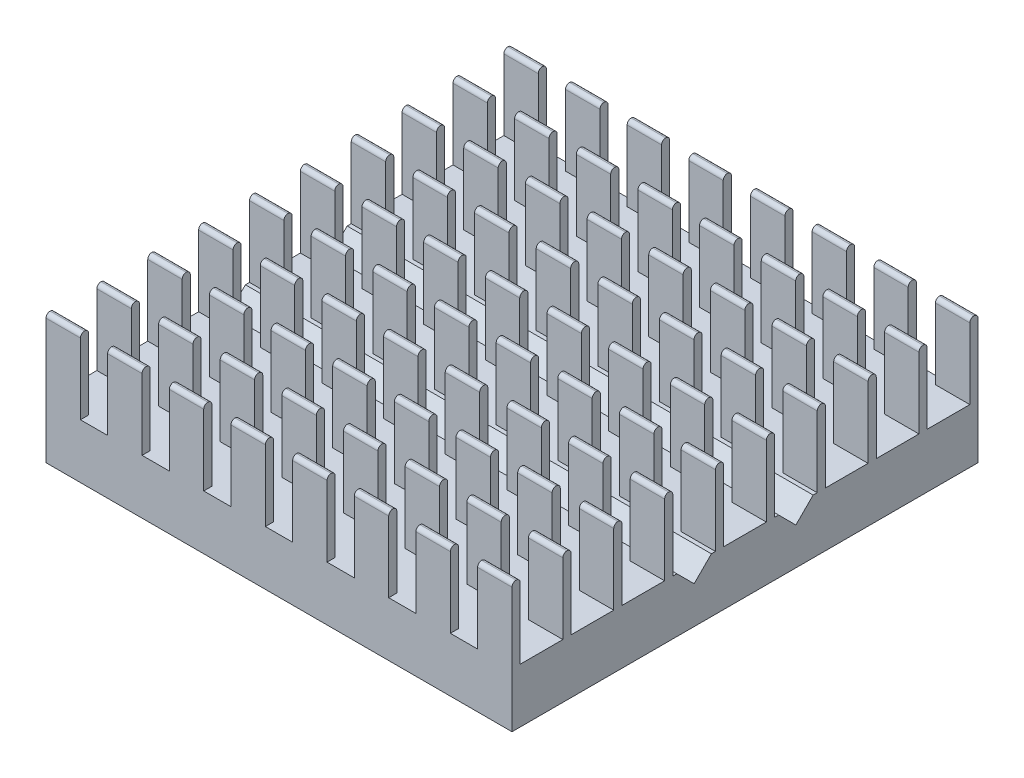
SolidWorks part; units mm, degrees
ref_plane "Front Plane" through (0, 0, 0) normal (0, 0, 1) x (1, 0, 0)
ref_plane "Top Plane" through (0, 0, 0) normal (0, 1, 0) x (1, 0, 0)
ref_plane "Right Plane" through (0, 0, 0) normal (1, 0, 0) x (0, 0, -1)
sketch "Sketch1" plane through (0, 0, 0) normal (1, 0, 0) x (0, 0, -1)
  line L0 (-17.125, -0.75) -> (17.125, -0.75) construction
  line L1 (-17.125, 4.75) -> (17.125, 4.75)
  line L2 (-17.125, 4.75) -> (-17.125, -4.75)
  line L3 (-17.125, -4.75) -> (17.125, -4.75)
  line L4 (17.125, 4.75) -> (17.125, -4.75)
  point P4 (-17.125, 0)
  point P6 (0, 4.75)
  dimension "Overall Length" = 34.25
  dimension "Overall Height" = 9.5
  dimension "Base Height" = 4
sketch "Sketch2" plane through (0, 0, 0) normal (0, 1, 0) x (1, 0, 0)
  line L0 (-12.5936, -16.525) -> (-10.0636, -16.525)
  line L1 (-17.125, 17.125) -> (17.125, 17.125) construction
  line L2 (-17.125, 17.125) -> (-17.125, -17.125) construction
  line L3 (-17.125, -17.125) -> (17.125, -17.125) construction
  line L4 (17.125, 17.125) -> (17.125, -17.125) construction
  line L5 (-17.125, -16.525) -> (-14.595, -16.525)
  line L6 (-17.125, -16.525) -> (-17.125, -17.125)
  line L7 (-17.125, -17.125) -> (-14.595, -17.125)
  line L8 (-14.595, -16.525) -> (-14.595, -17.125)
  line L9 (-12.5936, -16.525) -> (-12.5936, -17.125)
  line L10 (-12.5936, -17.125) -> (-10.0636, -17.125)
  line L11 (-10.0636, -16.525) -> (-10.0636, -17.125)
  line L12 (-8.0621, -16.525) -> (-5.5321, -16.525)
  line L13 (-8.0621, -16.525) -> (-8.0621, -17.125)
  line L14 (-8.0621, -17.125) -> (-5.5321, -17.125)
  line L15 (-5.5321, -16.525) -> (-5.5321, -17.125)
  line L16 (-12.5936, -12.7861) -> (-10.0636, -12.7861)
  line L17 (-12.5936, -12.7861) -> (-12.5936, -13.3861)
  line L18 (-12.5936, -13.3861) -> (-10.0636, -13.3861)
  line L19 (-10.0636, -12.7861) -> (-10.0636, -13.3861)
  line L20 (-8.0621, -12.7861) -> (-5.5321, -12.7861)
  line L21 (-8.0621, -12.7861) -> (-8.0621, -13.3861)
  line L22 (-8.0621, -13.3861) -> (-5.5321, -13.3861)
  line L23 (-5.5321, -12.7861) -> (-5.5321, -13.3861)
  line L24 (-12.5936, -9.0472) -> (-10.0636, -9.0472)
  line L25 (-12.5936, -9.0472) -> (-12.5936, -9.6472)
  line L26 (-12.5936, -9.6472) -> (-10.0636, -9.6472)
  line L27 (-10.0636, -9.0472) -> (-10.0636, -9.6472)
  line L28 (-8.0621, -9.0472) -> (-5.5321, -9.0472)
  line L29 (-8.0621, -9.0472) -> (-8.0621, -9.6472)
  line L30 (-8.0621, -9.6472) -> (-5.5321, -9.6472)
  line L31 (-5.5321, -9.0472) -> (-5.5321, -9.6472)
  line L32 (-12.5936, -5.3083) -> (-10.0636, -5.3083)
  line L33 (-12.5936, -5.3083) -> (-12.5936, -5.9083)
  line L34 (-12.5936, -5.9083) -> (-10.0636, -5.9083)
  line L35 (-10.0636, -5.3083) -> (-10.0636, -5.9083)
  line L36 (-8.0621, -5.3083) -> (-5.5321, -5.3083)
  line L37 (-8.0621, -5.3083) -> (-8.0621, -5.9083)
  line L38 (-8.0621, -5.9083) -> (-5.5321, -5.9083)
  line L39 (-5.5321, -5.3083) -> (-5.5321, -5.9083)
  line L40 (-12.5936, -1.5694) -> (-10.0636, -1.5694)
  line L41 (-12.5936, -1.5694) -> (-12.5936, -2.1694)
  line L42 (-12.5936, -2.1694) -> (-10.0636, -2.1694)
  line L43 (-10.0636, -1.5694) -> (-10.0636, -2.1694)
  line L44 (-8.0621, -1.5694) -> (-5.5321, -1.5694)
  line L45 (-8.0621, -1.5694) -> (-8.0621, -2.1694)
  line L46 (-8.0621, -2.1694) -> (-5.5321, -2.1694)
  line L47 (-5.5321, -1.5694) -> (-5.5321, -2.1694)
  line L48 (-12.5936, 2.1694) -> (-10.0636, 2.1694)
  line L49 (-12.5936, 2.1694) -> (-12.5936, 1.5694)
  line L50 (-12.5936, 1.5694) -> (-10.0636, 1.5694)
  line L51 (-10.0636, 2.1694) -> (-10.0636, 1.5694)
  line L52 (-8.0621, 2.1694) -> (-5.5321, 2.1694)
  line L53 (-8.0621, 2.1694) -> (-8.0621, 1.5694)
  line L54 (-8.0621, 1.5694) -> (-5.5321, 1.5694)
  line L55 (-5.5321, 2.1694) -> (-5.5321, 1.5694)
  line L56 (-17.125, -12.7861) -> (-14.595, -12.7861)
  line L57 (-17.125, -12.7861) -> (-17.125, -13.3861)
  line L58 (-17.125, -13.3861) -> (-14.595, -13.3861)
  line L59 (-14.595, -12.7861) -> (-14.595, -13.3861)
  line L60 (-17.125, -9.0472) -> (-14.595, -9.0472)
  line L61 (-17.125, -9.0472) -> (-17.125, -9.6472)
  line L62 (-17.125, -9.6472) -> (-14.595, -9.6472)
  line L63 (-14.595, -9.0472) -> (-14.595, -9.6472)
  line L64 (-17.125, -5.3083) -> (-14.595, -5.3083)
  line L65 (-17.125, -5.3083) -> (-17.125, -5.9083)
  line L66 (-17.125, -5.9083) -> (-14.595, -5.9083)
  line L67 (-14.595, -5.3083) -> (-14.595, -5.9083)
  line L68 (-17.125, -1.5694) -> (-14.595, -1.5694)
  line L69 (-17.125, -1.5694) -> (-17.125, -2.1694)
  line L70 (-17.125, -2.1694) -> (-14.595, -2.1694)
  line L71 (-14.595, -1.5694) -> (-14.595, -2.1694)
  line L72 (-17.125, 2.1694) -> (-14.595, 2.1694)
  line L73 (-17.125, 2.1694) -> (-17.125, 1.5694)
  line L74 (-17.125, 1.5694) -> (-14.595, 1.5694)
  line L75 (-14.595, 2.1694) -> (-14.595, 1.5694)
  line L76 (-17.125, -16.525) -> (-12.5936, -16.525) construction
  line L77 (-17.125, -16.525) -> (-17.125, -12.7861) construction
  line L78 (-17.125, 13.3861) -> (-14.595, 13.3861)
  line L79 (-17.125, 13.3861) -> (-17.125, 12.7861)
  line L80 (-17.125, 12.7861) -> (-14.595, 12.7861)
  line L81 (-3.5307, -16.525) -> (-1.0007, -16.525)
  line L82 (-3.5307, -16.525) -> (-3.5307, -17.125)
  line L83 (-3.5307, -17.125) -> (-1.0007, -17.125)
  line L84 (-1.0007, -16.525) -> (-1.0007, -17.125)
  line L85 (-3.5307, -12.7861) -> (-1.0007, -12.7861)
  line L86 (-3.5307, -12.7861) -> (-3.5307, -13.3861)
  line L87 (-3.5307, -13.3861) -> (-1.0007, -13.3861)
  line L88 (-1.0007, -12.7861) -> (-1.0007, -13.3861)
  line L89 (-3.5307, -9.0472) -> (-1.0007, -9.0472)
  line L90 (-3.5307, -9.0472) -> (-3.5307, -9.6472)
  line L91 (-3.5307, -9.6472) -> (-1.0007, -9.6472)
  line L92 (-1.0007, -9.0472) -> (-1.0007, -9.6472)
  line L93 (-3.5307, -5.3083) -> (-1.0007, -5.3083)
  line L94 (-3.5307, -5.3083) -> (-3.5307, -5.9083)
  line L95 (-3.5307, -5.9083) -> (-1.0007, -5.9083)
  line L96 (-1.0007, -5.3083) -> (-1.0007, -5.9083)
  line L97 (-3.5307, -1.5694) -> (-1.0007, -1.5694)
  line L98 (-3.5307, -1.5694) -> (-3.5307, -2.1694)
  line L99 (-3.5307, -2.1694) -> (-1.0007, -2.1694)
  line L100 (-1.0007, -1.5694) -> (-1.0007, -2.1694)
  line L101 (-3.5307, 2.1694) -> (-1.0007, 2.1694)
  line L102 (-3.5307, 2.1694) -> (-3.5307, 1.5694)
  line L103 (-3.5307, 1.5694) -> (-1.0007, 1.5694)
  line L104 (-1.0007, 2.1694) -> (-1.0007, 1.5694)
  line L105 (-17.125, 5.9083) -> (-14.595, 5.9083)
  line L106 (-17.125, 5.9083) -> (-17.125, 5.3083)
  line L107 (-17.125, 5.3083) -> (-14.595, 5.3083)
  line L108 (-14.595, 5.9083) -> (-14.595, 5.3083)
  line L109 (-12.5936, 5.9083) -> (-10.0636, 5.9083)
  line L110 (-12.5936, 5.9083) -> (-12.5936, 5.3083)
  line L111 (-12.5936, 5.3083) -> (-10.0636, 5.3083)
  line L112 (-10.0636, 5.9083) -> (-10.0636, 5.3083)
  line L113 (-8.0621, 5.9083) -> (-5.5321, 5.9083)
  line L114 (-8.0621, 5.9083) -> (-8.0621, 5.3083)
  line L115 (-8.0621, 5.3083) -> (-5.5321, 5.3083)
  line L116 (-5.5321, 5.9083) -> (-5.5321, 5.3083)
  line L117 (-3.5307, 5.9083) -> (-1.0007, 5.9083)
  line L118 (-3.5307, 5.9083) -> (-3.5307, 5.3083)
  line L119 (-3.5307, 5.3083) -> (-1.0007, 5.3083)
  line L120 (-1.0007, 5.9083) -> (-1.0007, 5.3083)
  line L121 (-17.125, 9.6472) -> (-14.595, 9.6472)
  line L122 (-17.125, 9.6472) -> (-17.125, 9.0472)
  line L123 (-17.125, 9.0472) -> (-14.595, 9.0472)
  line L124 (-14.595, 9.6472) -> (-14.595, 9.0472)
  line L125 (-12.5936, 9.6472) -> (-10.0636, 9.6472)
  line L126 (-12.5936, 9.6472) -> (-12.5936, 9.0472)
  line L127 (-12.5936, 9.0472) -> (-10.0636, 9.0472)
  line L128 (-10.0636, 9.6472) -> (-10.0636, 9.0472)
  line L129 (-8.0621, 9.6472) -> (-5.5321, 9.6472)
  line L130 (-8.0621, 9.6472) -> (-8.0621, 9.0472)
  line L131 (-8.0621, 9.0472) -> (-5.5321, 9.0472)
  line L132 (-5.5321, 9.6472) -> (-5.5321, 9.0472)
  line L133 (-3.5307, 9.6472) -> (-1.0007, 9.6472)
  line L134 (-3.5307, 9.6472) -> (-3.5307, 9.0472)
  line L135 (-3.5307, 9.0472) -> (-1.0007, 9.0472)
  line L136 (-1.0007, 9.6472) -> (-1.0007, 9.0472)
  line L137 (1.0007, -16.525) -> (3.5307, -16.525)
  line L138 (1.0007, -16.525) -> (1.0007, -17.125)
  line L139 (1.0007, -17.125) -> (3.5307, -17.125)
  line L140 (3.5307, -16.525) -> (3.5307, -17.125)
  line L141 (1.0007, -12.7861) -> (3.5307, -12.7861)
  line L142 (1.0007, -12.7861) -> (1.0007, -13.3861)
  line L143 (1.0007, -13.3861) -> (3.5307, -13.3861)
  line L144 (3.5307, -12.7861) -> (3.5307, -13.3861)
  line L145 (1.0007, -9.0472) -> (3.5307, -9.0472)
  line L146 (1.0007, -9.0472) -> (1.0007, -9.6472)
  line L147 (1.0007, -9.6472) -> (3.5307, -9.6472)
  line L148 (3.5307, -9.0472) -> (3.5307, -9.6472)
  line L149 (1.0007, -5.3083) -> (3.5307, -5.3083)
  line L150 (1.0007, -5.3083) -> (1.0007, -5.9083)
  line L151 (1.0007, -5.9083) -> (3.5307, -5.9083)
  line L152 (3.5307, -5.3083) -> (3.5307, -5.9083)
  line L153 (1.0007, -1.5694) -> (3.5307, -1.5694)
  line L154 (1.0007, -1.5694) -> (1.0007, -2.1694)
  line L155 (1.0007, -2.1694) -> (3.5307, -2.1694)
  line L156 (3.5307, -1.5694) -> (3.5307, -2.1694)
  line L157 (1.0007, 2.1694) -> (3.5307, 2.1694)
  line L158 (1.0007, 2.1694) -> (1.0007, 1.5694)
  line L159 (1.0007, 1.5694) -> (3.5307, 1.5694)
  line L160 (3.5307, 2.1694) -> (3.5307, 1.5694)
  line L161 (1.0007, 5.9083) -> (3.5307, 5.9083)
  line L162 (1.0007, 5.9083) -> (1.0007, 5.3083)
  line L163 (1.0007, 5.3083) -> (3.5307, 5.3083)
  line L164 (3.5307, 5.9083) -> (3.5307, 5.3083)
  line L165 (1.0007, 9.6472) -> (3.5307, 9.6472)
  line L166 (1.0007, 9.6472) -> (1.0007, 9.0472)
  line L167 (1.0007, 9.0472) -> (3.5307, 9.0472)
  line L168 (3.5307, 9.6472) -> (3.5307, 9.0472)
  line L169 (0, -1.8694) -> (0, 1.8694) construction
  line L170 (0, -1.8694) -> (0, -5.6083) construction
  line L171 (0, 1.8694) -> (0, 5.6083) construction
  line L172 (0, -1.8694) -> (0, -2.4694) construction
  line L173 (0, -5.6083) -> (0, -5.0083) construction
  line L174 (0, 5.6083) -> (0, 5.0083) construction
  line L175 (0, 1.8694) -> (0, 2.4694) construction
  line L176 (-14.595, 13.3861) -> (-14.595, 12.7861)
  line L177 (-12.5936, 13.3861) -> (-10.0636, 13.3861)
  line L178 (-12.5936, 13.3861) -> (-12.5936, 12.7861)
  line L179 (-12.5936, 12.7861) -> (-10.0636, 12.7861)
  line L180 (-10.0636, 13.3861) -> (-10.0636, 12.7861)
  line L181 (-8.0621, 13.3861) -> (-5.5321, 13.3861)
  line L182 (-8.0621, 13.3861) -> (-8.0621, 12.7861)
  line L183 (-8.0621, 12.7861) -> (-5.5321, 12.7861)
  line L184 (-5.5321, 13.3861) -> (-5.5321, 12.7861)
  line L185 (-3.5307, 13.3861) -> (-1.0007, 13.3861)
  line L186 (-3.5307, 13.3861) -> (-3.5307, 12.7861)
  line L187 (-3.5307, 12.7861) -> (-1.0007, 12.7861)
  line L188 (-1.0007, 13.3861) -> (-1.0007, 12.7861)
  line L189 (1.0007, 13.3861) -> (3.5307, 13.3861)
  line L190 (1.0007, 13.3861) -> (1.0007, 12.7861)
  line L191 (1.0007, 12.7861) -> (3.5307, 12.7861)
  line L192 (3.5307, 13.3861) -> (3.5307, 12.7861)
  line L193 (-17.125, 17.125) -> (-14.595, 17.125)
  line L194 (-17.125, 17.125) -> (-17.125, 16.525)
  line L195 (-17.125, 16.525) -> (-14.595, 16.525)
  line L196 (-14.595, 17.125) -> (-14.595, 16.525)
  line L197 (-12.5936, 17.125) -> (-10.0636, 17.125)
  line L198 (-12.5936, 17.125) -> (-12.5936, 16.525)
  line L199 (-12.5936, 16.525) -> (-10.0636, 16.525)
  line L200 (-10.0636, 17.125) -> (-10.0636, 16.525)
  line L201 (-8.0621, 17.125) -> (-5.5321, 17.125)
  line L202 (-8.0621, 17.125) -> (-8.0621, 16.525)
  line L203 (-8.0621, 16.525) -> (-5.5321, 16.525)
  line L204 (-5.5321, 17.125) -> (-5.5321, 16.525)
  line L205 (-3.5307, 17.125) -> (-1.0007, 17.125)
  line L206 (-3.5307, 17.125) -> (-3.5307, 16.525)
  line L207 (-3.5307, 16.525) -> (-1.0007, 16.525)
  line L208 (-1.0007, 17.125) -> (-1.0007, 16.525)
  line L209 (1.0007, 17.125) -> (3.5307, 17.125)
  line L210 (1.0007, 17.125) -> (1.0007, 16.525)
  line L211 (1.0007, 16.525) -> (3.5307, 16.525)
  line L212 (3.5307, 17.125) -> (3.5307, 16.525)
  line L213 (5.5321, -16.525) -> (8.0621, -16.525)
  line L214 (5.5321, -16.525) -> (5.5321, -17.125)
  line L215 (5.5321, -17.125) -> (8.0621, -17.125)
  line L216 (8.0621, -16.525) -> (8.0621, -17.125)
  line L217 (10.0636, -16.525) -> (12.5936, -16.525)
  line L218 (10.0636, -16.525) -> (10.0636, -17.125)
  line L219 (10.0636, -17.125) -> (12.5936, -17.125)
  line L220 (12.5936, -16.525) -> (12.5936, -17.125)
  line L221 (14.595, -16.525) -> (17.125, -16.525)
  line L222 (14.595, -16.525) -> (14.595, -17.125)
  line L223 (14.595, -17.125) -> (17.125, -17.125)
  line L224 (17.125, -16.525) -> (17.125, -17.125)
  line L225 (5.5321, -12.7861) -> (8.0621, -12.7861)
  line L226 (5.5321, -12.7861) -> (5.5321, -13.3861)
  line L227 (5.5321, -13.3861) -> (8.0621, -13.3861)
  line L228 (8.0621, -12.7861) -> (8.0621, -13.3861)
  line L229 (10.0636, -12.7861) -> (12.5936, -12.7861)
  line L230 (10.0636, -12.7861) -> (10.0636, -13.3861)
  line L231 (10.0636, -13.3861) -> (12.5936, -13.3861)
  line L232 (12.5936, -12.7861) -> (12.5936, -13.3861)
  line L233 (14.595, -12.7861) -> (17.125, -12.7861)
  line L234 (14.595, -12.7861) -> (14.595, -13.3861)
  line L235 (14.595, -13.3861) -> (17.125, -13.3861)
  line L236 (17.125, -12.7861) -> (17.125, -13.3861)
  line L237 (5.5321, -9.0472) -> (8.0621, -9.0472)
  line L238 (5.5321, -9.0472) -> (5.5321, -9.6472)
  line L239 (5.5321, -9.6472) -> (8.0621, -9.6472)
  line L240 (8.0621, -9.0472) -> (8.0621, -9.6472)
  line L241 (10.0636, -9.0472) -> (12.5936, -9.0472)
  line L242 (10.0636, -9.0472) -> (10.0636, -9.6472)
  line L243 (10.0636, -9.6472) -> (12.5936, -9.6472)
  line L244 (12.5936, -9.0472) -> (12.5936, -9.6472)
  line L245 (14.595, -9.0472) -> (17.125, -9.0472)
  line L246 (14.595, -9.0472) -> (14.595, -9.6472)
  line L247 (14.595, -9.6472) -> (17.125, -9.6472)
  line L248 (17.125, -9.0472) -> (17.125, -9.6472)
  line L249 (5.5321, -5.3083) -> (8.0621, -5.3083)
  line L250 (5.5321, -5.3083) -> (5.5321, -5.9083)
  line L251 (5.5321, -5.9083) -> (8.0621, -5.9083)
  line L252 (8.0621, -5.3083) -> (8.0621, -5.9083)
  line L253 (10.0636, -5.3083) -> (12.5936, -5.3083)
  line L254 (10.0636, -5.3083) -> (10.0636, -5.9083)
  line L255 (10.0636, -5.9083) -> (12.5936, -5.9083)
  line L256 (12.5936, -5.3083) -> (12.5936, -5.9083)
  line L257 (14.595, -5.3083) -> (17.125, -5.3083)
  line L258 (14.595, -5.3083) -> (14.595, -5.9083)
  line L259 (14.595, -5.9083) -> (17.125, -5.9083)
  line L260 (17.125, -5.3083) -> (17.125, -5.9083)
  line L261 (5.5321, -1.5694) -> (8.0621, -1.5694)
  line L262 (5.5321, -1.5694) -> (5.5321, -2.1694)
  line L263 (5.5321, -2.1694) -> (8.0621, -2.1694)
  line L264 (8.0621, -1.5694) -> (8.0621, -2.1694)
  line L265 (10.0636, -1.5694) -> (12.5936, -1.5694)
  line L266 (10.0636, -1.5694) -> (10.0636, -2.1694)
  line L267 (10.0636, -2.1694) -> (12.5936, -2.1694)
  line L268 (12.5936, -1.5694) -> (12.5936, -2.1694)
  line L269 (14.595, -1.5694) -> (17.125, -1.5694)
  line L270 (14.595, -1.5694) -> (14.595, -2.1694)
  line L271 (14.595, -2.1694) -> (17.125, -2.1694)
  line L272 (17.125, -1.5694) -> (17.125, -2.1694)
  line L273 (5.5321, 2.1694) -> (8.0621, 2.1694)
  line L274 (5.5321, 2.1694) -> (5.5321, 1.5694)
  line L275 (5.5321, 1.5694) -> (8.0621, 1.5694)
  line L276 (8.0621, 2.1694) -> (8.0621, 1.5694)
  line L277 (10.0636, 2.1694) -> (12.5936, 2.1694)
  line L278 (10.0636, 2.1694) -> (10.0636, 1.5694)
  line L279 (10.0636, 1.5694) -> (12.5936, 1.5694)
  line L280 (12.5936, 2.1694) -> (12.5936, 1.5694)
  line L281 (14.595, 2.1694) -> (17.125, 2.1694)
  line L282 (14.595, 2.1694) -> (14.595, 1.5694)
  line L283 (14.595, 1.5694) -> (17.125, 1.5694)
  line L284 (17.125, 2.1694) -> (17.125, 1.5694)
  line L285 (5.5321, 5.9083) -> (8.0621, 5.9083)
  line L286 (5.5321, 5.9083) -> (5.5321, 5.3083)
  line L287 (5.5321, 5.3083) -> (8.0621, 5.3083)
  line L288 (8.0621, 5.9083) -> (8.0621, 5.3083)
  line L289 (10.0636, 5.9083) -> (12.5936, 5.9083)
  line L290 (10.0636, 5.9083) -> (10.0636, 5.3083)
  line L291 (10.0636, 5.3083) -> (12.5936, 5.3083)
  line L292 (12.5936, 5.9083) -> (12.5936, 5.3083)
  line L293 (14.595, 5.9083) -> (17.125, 5.9083)
  line L294 (14.595, 5.9083) -> (14.595, 5.3083)
  line L295 (14.595, 5.3083) -> (17.125, 5.3083)
  line L296 (17.125, 5.9083) -> (17.125, 5.3083)
  line L297 (5.5321, 9.6472) -> (8.0621, 9.6472)
  line L298 (5.5321, 9.6472) -> (5.5321, 9.0472)
  line L299 (5.5321, 9.0472) -> (8.0621, 9.0472)
  line L300 (8.0621, 9.6472) -> (8.0621, 9.0472)
  line L301 (10.0636, 9.6472) -> (12.5936, 9.6472)
  line L302 (10.0636, 9.6472) -> (10.0636, 9.0472)
  line L303 (10.0636, 9.0472) -> (12.5936, 9.0472)
  line L304 (12.5936, 9.6472) -> (12.5936, 9.0472)
  line L305 (14.595, 9.6472) -> (17.125, 9.6472)
  line L306 (14.595, 9.6472) -> (14.595, 9.0472)
  line L307 (14.595, 9.0472) -> (17.125, 9.0472)
  line L308 (17.125, 9.6472) -> (17.125, 9.0472)
  line L309 (5.5321, 13.3861) -> (8.0621, 13.3861)
  line L310 (5.5321, 13.3861) -> (5.5321, 12.7861)
  line L311 (5.5321, 12.7861) -> (8.0621, 12.7861)
  line L312 (8.0621, 13.3861) -> (8.0621, 12.7861)
  line L313 (10.0636, 13.3861) -> (12.5936, 13.3861)
  line L314 (10.0636, 13.3861) -> (10.0636, 12.7861)
  line L315 (10.0636, 12.7861) -> (12.5936, 12.7861)
  line L316 (12.5936, 13.3861) -> (12.5936, 12.7861)
  line L317 (14.595, 13.3861) -> (17.125, 13.3861)
  line L318 (14.595, 13.3861) -> (14.595, 12.7861)
  line L319 (14.595, 12.7861) -> (17.125, 12.7861)
  line L320 (17.125, 13.3861) -> (17.125, 12.7861)
  line L321 (5.5321, 17.125) -> (8.0621, 17.125)
  line L322 (5.5321, 17.125) -> (5.5321, 16.525)
  line L323 (5.5321, 16.525) -> (8.0621, 16.525)
  line L324 (8.0621, 17.125) -> (8.0621, 16.525)
  line L325 (10.0636, 17.125) -> (12.5936, 17.125)
  line L326 (10.0636, 17.125) -> (10.0636, 16.525)
  line L327 (10.0636, 16.525) -> (12.5936, 16.525)
  line L328 (12.5936, 17.125) -> (12.5936, 16.525)
  line L329 (14.595, 17.125) -> (17.125, 17.125)
  line L330 (14.595, 17.125) -> (14.595, 16.525)
  line L331 (14.595, 16.525) -> (17.125, 16.525)
  line L332 (17.125, 17.125) -> (17.125, 16.525)
  point P174 (0, 0)
  point P177 (0, -3.7389)
  point P179 (0, 3.7389)
  dimension "Overall Width" = 34.25
  dimension "Fin Width" = 2.53
  dimension "Fin Length" = 0.6
  dimension "Fin Width Spacing" = 4.5314
  dimension "Fin Length Spacing" = 3.7389
  dimension "Fin Width Count" = 8
  dimension "Fin Length Count" = 10
sketch "Sketch3" plane through (0, 0, 0) normal (0, 1, 0) x (1, 0, 0)
  line L0 (-17.125, 17.125) -> (17.125, 17.125) construction
  line L1 (-17.125, -17.125) -> (17.125, -17.125) construction
  line L2 (17.125, 17.125) -> (17.125, -17.125) construction
  line L3 (-17.125, 17.125) -> (-17.125, -17.125) construction
  line L4 (-17.125, 17.125) -> (17.125, 17.125)
  line L5 (-17.125, -17.125) -> (17.125, -17.125)
  line L6 (17.125, 17.125) -> (17.125, -17.125)
  line L7 (-17.125, 17.125) -> (-17.125, -17.125)
extrude "Boss-Extrude1" add sketch "Sketch3" along normal up to vertex (-0.75 mm away) from vertex up to point (0, -0.75, 17.125) starting at point (0, -4.75, 17.125)
sketch "Sketch4" plane through (0, 0, 0) normal (0, 1, 0) x (1, 0, 0)
  line L0 (-14.595, -16.525) -> (-14.595, -17.125) construction
  line L1 (-17.125, -17.125) -> (-14.595, -17.125) construction
  line L2 (-17.125, -16.525) -> (-14.595, -16.525) construction
  line L3 (-17.125, -16.525) -> (-17.125, -17.125) construction
  line L4 (-14.595, -16.525) -> (-14.595, -17.125)
  line L5 (-17.125, -17.125) -> (-14.595, -17.125)
  line L6 (-17.125, -16.525) -> (-14.595, -16.525)
  line L7 (-17.125, -16.525) -> (-17.125, -17.125)
extrude "Boss-Extrude2" add sketch "Sketch4" along normal up to vertex (4.75 mm away) from vertex up to point (0, 4.75, 17.125) starting at point (0, -0.75, 17.125)
fillet "Fillet1" radius 0.3 2 edges at (-15.86, 4.75, 16.525) (-15.86, 4.75, 17.125)
pattern_linear "LPattern1" count 8 spacing 4.5314 along (1, 0, 0) count 10 spacing 3.7389 along (0, 0, -1) of "Boss-Extrude2", "Fillet1"
sketch "Sketch5" plane through (0, 0, 0) normal (1, 0, 0) x (0, 0, -1)
  line L0 (-5.0083, -0.75) -> (-3.7389, -2.0194)
  line L1 (-3.7389, -2.0194) -> (-2.4694, -0.75)
  line L2 (-5.0083, -0.75) -> (-2.4694, -0.75)
  line L3 (-17.125, -0.75) -> (17.125, -0.75) construction
  line L4 (0, -4.75) -> (0, 4.75) construction
  line L5 (-17.125, 4.75) -> (17.125, 4.75) construction
  line L6 (5.0083, -0.75) -> (2.4694, -0.75)
  line L7 (3.7389, -2.0194) -> (2.4694, -0.75)
  line L8 (5.0083, -0.75) -> (3.7389, -2.0194)
  point P12 (-3.7389, -0.75)
extrude "Cut-Extrude1" cut sketch "Sketch5" against normal through all both and the other way through all
equation "\"Fin Width Spacing@Sketch2\" =  (  ( \"Overall Width@Sketch2\" -  ( \"Fin Width@Sketch2\" * \"Fin Width Count@Sketch2\" )  )  /  ( \"Fin Width Count@Sketch2\" - 1 )  )  + \"Fin Width@Sketch2\""
equation "\"Fin Length Spacing@Sketch2\"=(  ( \"Overall Length@Sketch1\" -  ( \"Fin Length@Sketch2\" * \"Fin Length Count@Sketch2\" )  )  /  ( \"Fin Length Count@Sketch2\" - 1 )  )  + \"Fin Length@Sketch2\""
equation "\"D3@LPattern1\"=\"Fin Width Spacing@Sketch2\""
equation "\"D4@LPattern1\"=\"Fin Length Spacing@Sketch2\""
equation "\"D1@LPattern1\"=\"Fin Width Count@Sketch2\""
equation "\"D2@LPattern1\"=\"Fin Length Count@Sketch2\""
equation "\"D1@Fillet1\"=.5*\"Fin Length@Sketch2\""
